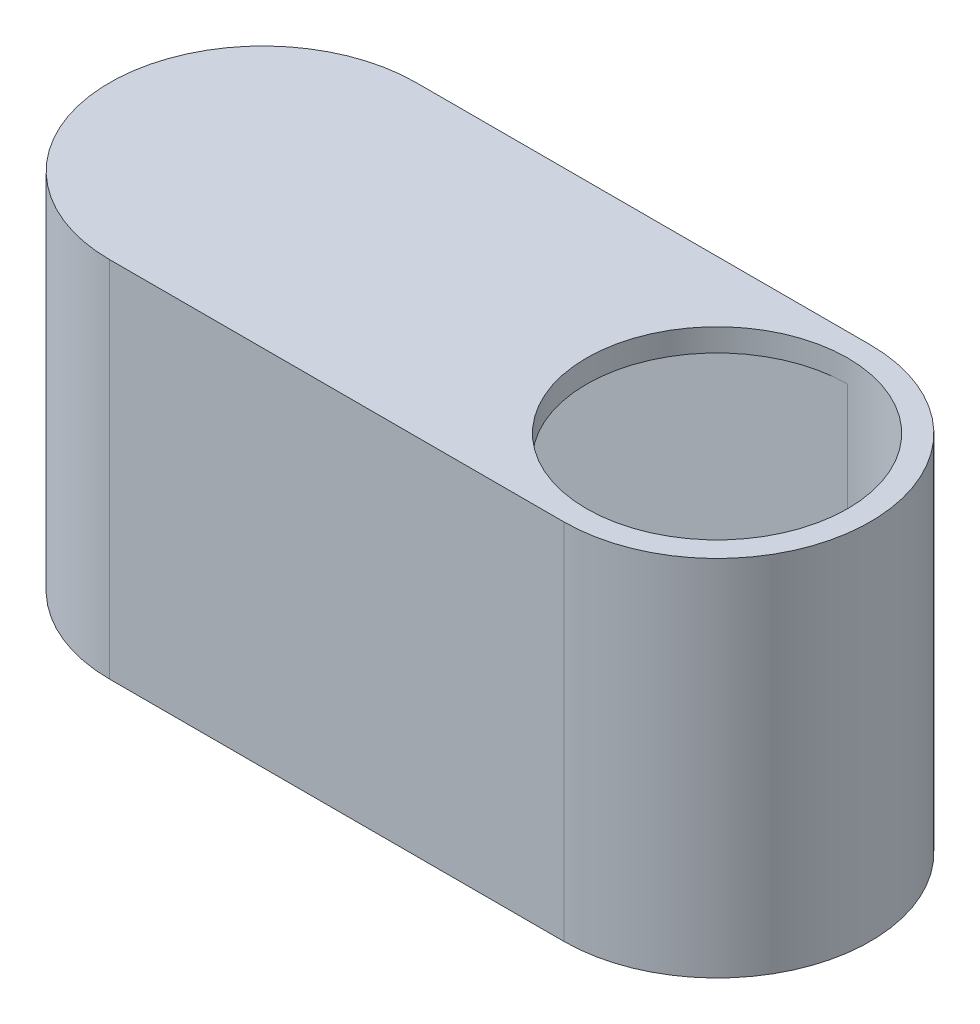
SolidWorks part; units mm, degrees
ref_plane "Front Plane" through (0, 0, 0) normal (0, 0, 1) x (1, 0, 0)
ref_plane "Top Plane" through (0, 0, 0) normal (0, 1, 0) x (1, 0, 0)
ref_plane "Right Plane" through (0, 0, 0) normal (1, 0, 0) x (0, 0, -1)
sketch "Sketch2" plane through (0, 0, 0) normal (0, 1, 0) x (1, 0, 0)
  line L0 (77.2984, 53.6856) -> (117.2984, 53.6856) construction
  line L1 (77.2984, 64.1856) -> (117.2984, 64.1856) construction
  line L2 (77.2984, 43.1856) -> (117.2984, 43.1856) construction
  line L3 (117.2984, 64.1856) -> (77.2984, 64.1856) construction
  line L4 (77.2984, 65.1856) -> (117.2984, 65.1856)
  line L5 (77.2984, 42.1856) -> (117.2984, 42.1856)
  line L6 (77.2984, 40.1856) -> (117.2984, 40.1856)
  line L7 (77.2984, 67.1856) -> (117.2984, 67.1856)
  arc A0 (77.2984, 64.1856) -> (77.2984, 43.1856) centre (77.2984, 53.6856) ccw construction
  arc A1 (117.2984, 43.1856) -> (117.2984, 64.1856) centre (117.2984, 53.6856) ccw construction
  arc A2 (77.2984, 64.1856) -> (77.2984, 43.1856) centre (77.2984, 53.6856) ccw construction
  arc A3 (117.2984, 42.1856) -> (117.2984, 65.1856) centre (117.2984, 53.6856) ccw
  arc A4 (77.2984, 65.1856) -> (77.2984, 42.1856) centre (77.2984, 53.6856) ccw
  arc A5 (77.2984, 67.1856) -> (77.2984, 40.1856) centre (77.2984, 53.6856) ccw
  arc A6 (117.2984, 40.1856) -> (117.2984, 67.1856) centre (117.2984, 53.6856) ccw
  point P2 (97.2984, 53.6856)
  dimension "D1" = 1
  dimension "D2" = 2
extrude "Boss-Extrude1" add sketch "Sketch2" along normal blind 30
sketch "Sketch3" plane through (0, 30, 0) normal (0, 1, 0) x (1, 0, 0)
  line L0 (77.2984, 53.6856) -> (117.2984, 53.6856) construction
  line L1 (77.2984, 67.1856) -> (117.2984, 67.1856)
  line L2 (77.2984, 40.1856) -> (117.2984, 40.1856)
  arc A0 (77.2984, 67.1856) -> (77.2984, 40.1856) centre (77.2984, 53.6856) ccw
  arc A1 (117.2984, 40.1856) -> (117.2984, 67.1856) centre (117.2984, 53.6856) ccw
  arc A2 (117.2984, 40.1856) -> (117.2984, 67.1856) centre (117.2984, 53.6856) ccw construction
  circle A3 centre (117.2984, 53.6856) radius 11.5
  point P4 (97.2984, 53.6856)
extrude "Boss-Extrude2" add sketch "Sketch3" along normal blind 2
